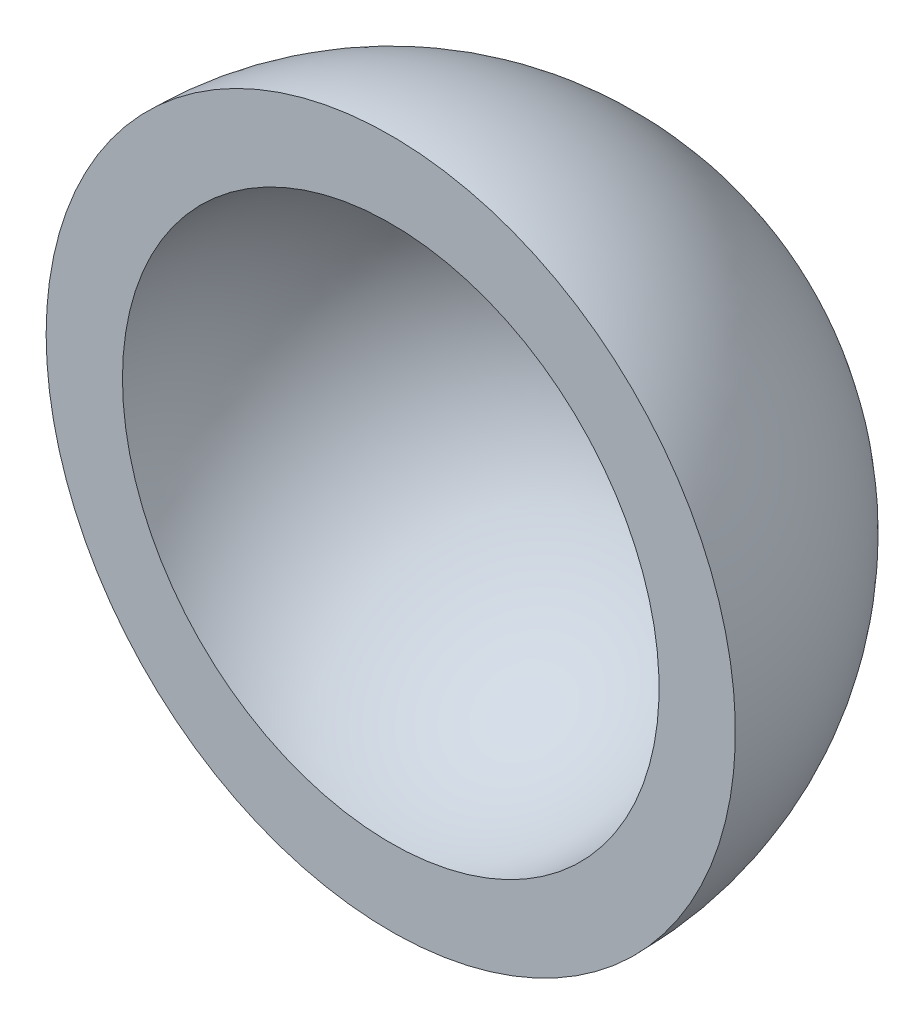
SolidWorks part; units mm, degrees
material "1060 Alloy"
ref_plane "Front Plane" through (0, 0, 0) normal (0, 0, 1) x (1, 0, 0)
ref_plane "Top Plane" through (0, 0, 0) normal (0, 1, 0) x (1, 0, 0)
ref_plane "Right Plane" through (0, 0, 0) normal (1, 0, 0) x (0, 0, -1)
sketch "Sketch1" plane through (0, 0, 0) normal (0, 0, 1) x (1, 0, 0)
  line L0 (0, -62.5) -> (0, 62.5)
  arc A0 (0, -62.5) -> (0, 62.5) centre (0, 0) ccw
  dimension "D1" = 125
ref_axis "Axis1" through (0, 68.75, 0) along (0, -1, 0)
revolve "Revolve5" add sketch "Sketch1" angle 180 about L0
sketch "Sketch2" plane through (0, 0, 0) normal (0, 0, 1) x (1, 0, 0)
  line L0 (0, -48.66) -> (0, 48.66)
  arc A0 (0, -48.66) -> (0, 48.66) centre (0, 0) ccw
  dimension "D1" = 97.32
revolve "Cut-Revolve1" cut sketch "Sketch2" angle 180 about L0
sketch "Sketch3" plane through (0, 0, 0) normal (0, 0, 1) x (1, 0, 0)
  point P0 (0, 0)
